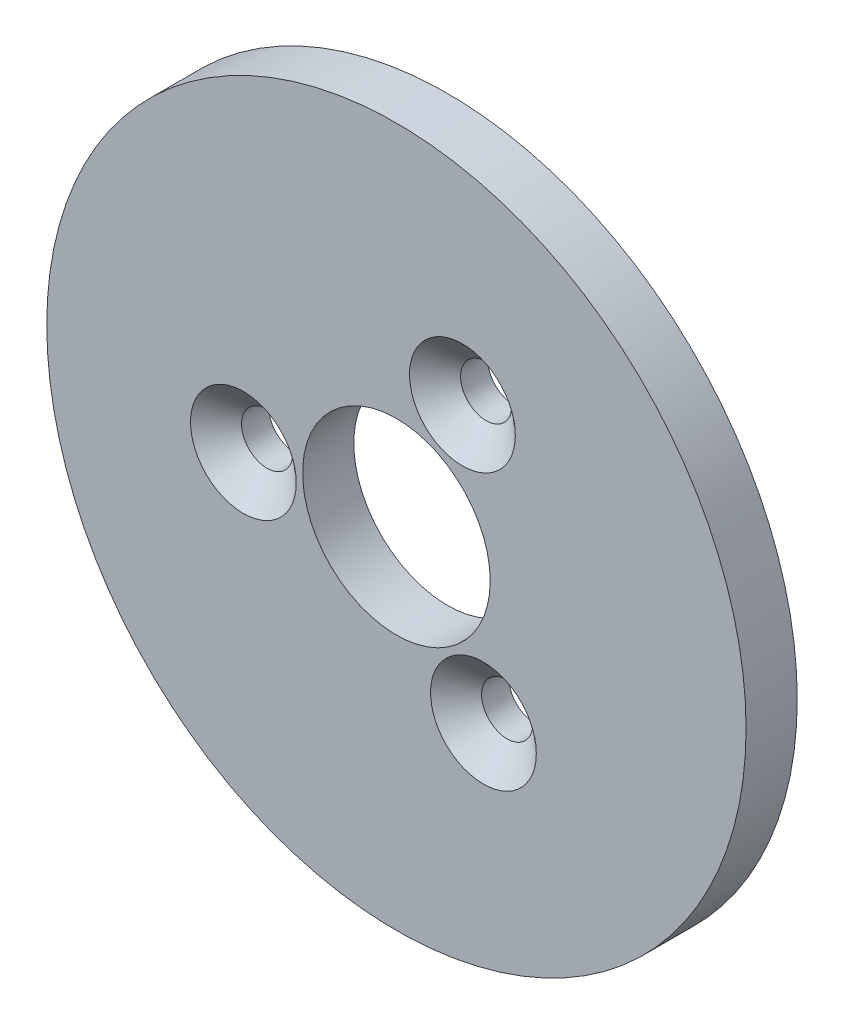
SolidWorks part; units mm, degrees
material "Acrylic (Medium-high impact)"
ref_plane "Front Plane" through (0, 0, 0) normal (0, 0, 1) x (1, 0, 0)
ref_plane "Top Plane" through (0, 0, 0) normal (0, 1, 0) x (1, 0, 0)
ref_plane "Right Plane" through (0, 0, 0) normal (1, 0, 0) x (0, 0, -1)
sketch "Sketch1" plane through (0, 0, 0) normal (0, 0, 1) x (1, 0, 0)
  circle A0 centre (0, 0) radius 20.5
  dimension "D1" = 41
extrude "Boss-Extrude1" add sketch "Sketch1" along normal blind 3
sketch "Sketch2" plane through (0, 0, 3) normal (0, 0, 1) x (1, 0, 0)
  circle A3 centre (-8.9719, -0.7111) radius 1.5
  circle A4 centre (-8.9719, -0.7111) radius 1.5
  circle A5 centre (5.1018, -7.4143) radius 1.5
  circle A6 centre (5.1018, -7.4143) radius 1.5
  circle A7 centre (3.8701, 8.1254) radius 1.5
  circle A8 centre (3.8701, 8.1254) radius 1.5
  dimension "D2" = 0
  dimension "D3" = 0
  dimension "D4" = 0
extrude "Cut-Extrude1" cut sketch "Sketch2" against normal through all
chamfer "Chamfer1" distance 1.6 angle 41 3 edges at (-7.4719, -0.7111, 3) (5.3701, 8.1254, 3) (6.6018, -7.4143, 3) first distance on face at (6.6018, -7.4143, 3)
sketch "Sketch3" plane through (0, 0, 3) normal (0, 0, 1) x (1, 0, 0)
  circle A1 centre (0, 0) radius 5.5
  circle A2 centre (0, 0) radius 5.5
  dimension "D1" = 0
extrude "Cut-Extrude2" cut sketch "Sketch3" against normal through all
equation "\"smallPulleyTeeth\"= 30"
equation "\"largePulleyTeeth\"= 30"
equation "\"eighthThick\"= 3.0mm"
equation "\"sixteenthThick\"= 1.7mm"
equation "\"quarterThick\"=6.0mm"
equation "\"OD\"= 145mm"
equation "\"puckAngle\"= 60.5deg"
equation "\"puckDiam\"= 76.5mm"
equation "\"axlePress\"= 5.9mm"
equation "\"press\"= 0.2mm"
equation "\"wheelClear\"= 0.3mm"
equation "\"10-32clear\"= 4.8mm"
equation "\"D1@Boss-Extrude1\"=\"eighthThick\""
equation "\"D1@Chamfer1\"=(6.5-\"6-32clear\")/2"
equation "\"6-32clear\"= 3.3mm"
equation "\"8-32clear\"= 4.0mm"
